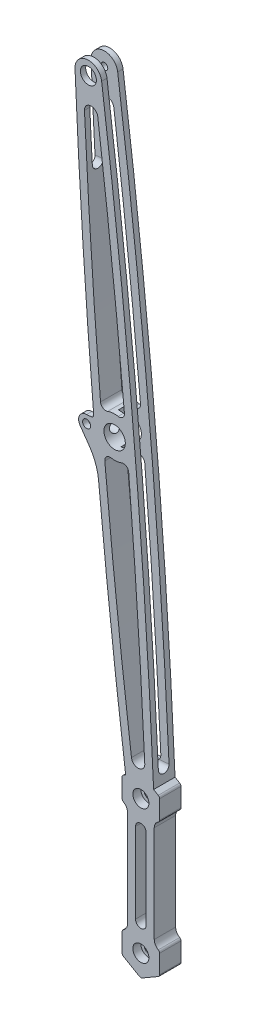
SolidWorks part; units mm, degrees
material "A2017"
ref_plane "正面" through (0, 0, 0) normal (0, 0, 1) x (1, 0, 0)
ref_plane "平面" through (0, 0, 0) normal (0, 1, 0) x (1, 0, 0)
ref_plane "右側面" through (0, 0, 0) normal (1, 0, 0) x (0, 0, -1)
sketch "ｽｹｯﾁ1" plane through (0, 0, 0) normal (0, 0, 1) x (1, 0, 0)
  line L0 (0, 0) -> (9.0749, 0) construction
  line L1 (0, 25) -> (0, 0) construction
  line L2 (0, -16.9171) -> (7, -20.9585)
  line L3 (7, 20.9585) -> (7, 29.0415)
  line L4 (7, 29.0415) -> (0, 33.0829)
  line L5 (0, 33.0829) -> (-7, 29.0415)
  line L6 (-7, 29.0415) -> (-7, 20.9585)
  line L7 (-7, 20.9585) -> (0, 16.9171)
  line L8 (0, 16.9171) -> (7, 20.9585)
  line L9 (-7, -20.9585) -> (0, -16.9171)
  line L10 (-7, -29.0415) -> (-7, -20.9585)
  line L11 (0, -33.0829) -> (-7, -29.0415)
  line L12 (7, -29.0415) -> (0, -33.0829)
  line L13 (7, -20.9585) -> (7, -29.0415)
  circle A0 centre (0, 25) radius 3
  circle A1 centre (0, -25) radius 3
  circle A2 centre (0, 25) radius 7 construction
  circle A3 centre (0, -25) radius 7 construction
  dimension "D1" = 6
  dimension "D2" = 50
  dimension "D3" = 14
extrude "ﾎﾞｽ - 押し出し1" add sketch "ｽｹｯﾁ1" along normal mid plane 8
sketch "ｽｹｯﾁ2" plane through (0, 0, 4) normal (0, 0, 1) x (1, 0, 0)
  line L0 (-7, 20.9585) -> (0, 16.9171) construction
  line L1 (5, -19.8038) -> (-5, -19.8038)
  line L2 (5, -19.8038) -> (5, 19.8038)
  line L3 (5, 19.8038) -> (-5, 19.8038)
  line L4 (-5, -19.8038) -> (-5, 19.8038)
  line L5 (5, -19.8038) -> (-5, 19.8038) construction
  line L6 (5, 19.8038) -> (-5, -19.8038) construction
  point P0 (0, 0)
  dimension "D1" = 10
extrude "ﾎﾞｽ - 押し出し2" add sketch "ｽｹｯﾁ2" against normal up to surface (8 mm away) up to face at (0, 25, -4)
fillet "ﾌｨﾚｯﾄ1" radius 3 4 edges at (5, -19.8038, 0) (-5, 19.8038, 0) (-5, -19.8038, 0) (5, 19.8038, 0)
fillet "ﾌｨﾚｯﾄ2" radius 1 10 edges at (-7, 20.9585, 0) (-7, 29.0415, 0) (0, 33.0829, 0) (7, 29.0415, 0) (7, 20.9585, 0) (7, -29.0415, 0) (0, -33.0829, 0) (-7, -29.0415, 0) (-7, -20.9585, 0) (7, -20.9585, 0)
sketch "ｽｹｯﾁ3" plane through (0, 0, -4) normal (0, 0, -1) x (-1, 0, 0)
  line L0 (0, -15) -> (0, 15) construction
  line L1 (-2, -15) -> (-2, 15)
  line L2 (2, -15) -> (2, 15)
  arc A0 (-2, -15) -> (2, -15) centre (0, -15) ccw
  arc A1 (2, 15) -> (-2, 15) centre (0, 15) ccw
  point P2 (0, 0)
  dimension "D1" = 4
  dimension "D2" = 30
extrude "ｶｯﾄ - 押し出し1" cut sketch "ｽｹｯﾁ3" against normal up to surface (8 mm away) up to face at (0, 0, 4)
sketch "ｽｹｯﾁ5" plane through (0, 0, 4) normal (0, 0, 1) x (1, 0, 0)
  circle A0 centre (0, -25) radius 3 construction
  circle A1 centre (0, 25) radius 3 construction
  circle A2 centre (0, -25) radius 3
  circle A3 centre (0, 25) radius 3
extrude "ﾎﾞｽ - 押し出し3" [suppressed] add sketch "ｽｹｯﾁ5" against normal blind 5
sketch "ｽｹｯﾁ8" plane through (0, 0, -4) normal (0, 0, -1) x (-1, 0, 0)
  circle A0 centre (0, -25) radius 3 construction
  circle A1 centre (0, 25) radius 3 construction
  circle A2 centre (0, -25) radius 3
  circle A3 centre (0, 25) radius 3
extrude "ﾎﾞｽ - 押し出し4" add sketch "ｽｹｯﾁ8" against normal blind 5
hole_wizard "M3 すきま穴1" positions "ｽｹｯﾁ6" profile "ｽｹｯﾁ7" hole size "M3" standard "JIS" end condition through all
sketch "ｽｹｯﾁ6" plane through (0, 0, 4) normal (0, 0, -1) x (-1, 0, 0)
  point P0 (0, 25)
  point P3 (0, -25)
sketch "ｽｹｯﾁ7" plane through (0, 25, 4) normal (1, 0, 0) x (0, -1, 0)
  line L0 (0, 0) -> (0, 8)
  line L1 (0, 8) -> (1.7, 8)
  line L2 (1.7, 8) -> (1.7, 0)
  line L5 (1.7, 0) -> (0, 0)
  line L11 (0, -6.35) -> (0, 107.95) construction
  dimension "通し穴の直径" = 3.4
  dimension "通し穴の深さ" = 8
sketch "ｽｹｯﾁ9" plane through (0, 0, 4) normal (0, 0, 1) x (1, 0, 0)
  line L0 (0, 25) -> (0, 298.9535) construction
  line L1 (0, 25) -> (-19.61, 249.1438) construction
  line L2 (0, 25) -> (-19.61, 249.1438) construction
  line L3 (-7.4715, 24.3463) -> (-27.0815, 248.4901) construction
  line L4 (7.4715, 25.6537) -> (-12.1386, 249.7975) construction
  line L15 (-7, 28.4641) -> (-7, 21.5359)
  line L16 (-5, 18.0718) -> (-5, -18.0718)
  line L17 (-7, -21.5359) -> (-7, -28.4641)
  line L18 (-6.5, -29.3301) -> (-0.5, -32.7942)
  line L19 (0.5, -32.7942) -> (6.5, -29.3301)
  line L20 (7, -28.4641) -> (7, -21.5359)
  line L21 (5, -18.0718) -> (5, 18.0718)
  line L22 (7, 21.5359) -> (7, 28.4641)
  line L23 (6.5, 29.3301) -> (0.5, 32.7942)
  line L24 (-0.5, 32.7942) -> (-6.5, 29.3301)
  line L25 (-7, 28.4641) -> (-7, 21.5359)
  line L26 (-5, 18.0718) -> (-5, -18.0718)
  line L27 (-7, -21.5359) -> (-7, -28.4641)
  line L28 (-6.5, -29.3301) -> (-0.5, -32.7942)
  line L29 (0.5, -32.7942) -> (6.5, -29.3301)
  line L30 (7, -28.4641) -> (7, -21.5359)
  line L31 (5, -18.0718) -> (5, 18.0718)
  line L32 (7, 21.5359) -> (7, 28.4641)
  line L33 (6.5, 29.3301) -> (0.5, 32.7942)
  line L34 (-0.5, 32.7942) -> (-6.5, 29.3301)
  arc A0 (-7.4715, 24.3463) -> (7.4715, 25.6537) centre (0, 25) ccw construction
  arc A1 (-12.1386, 249.7975) -> (-27.0815, 248.4901) centre (-19.61, 249.1438) ccw construction
  circle A2 centre (-19.61, 249.1438) radius 5 construction
  circle A3 centre (0, 25) radius 5
  arc A4 (-14.6533, 249.8004) -> (4.9954, 25.2141) centre (-2530.1776, -83.4321) cw
  arc A5 (-24.6055, 248.9297) -> (-4.9567, 24.3434) centre (2510.5676, 357.5759) ccw
  arc A6 (-14.6533, 249.8004) -> (-24.6055, 248.9297) centre (-19.61, 249.1438) ccw
  arc A16 (-7, 21.5359) -> (-6.5, 20.6699) centre (-6, 21.5359) ccw
  arc A17 (-5, 18.0718) -> (-6.5, 20.6699) centre (-8, 18.0718) ccw
  arc A18 (-6.5, -20.6699) -> (-5, -18.0718) centre (-8, -18.0718) ccw
  arc A19 (-6.5, -20.6699) -> (-7, -21.5359) centre (-6, -21.5359) ccw
  arc A20 (-7, -28.4641) -> (-6.5, -29.3301) centre (-6, -28.4641) ccw
  arc A21 (-0.5, -32.7942) -> (0.5, -32.7942) centre (0, -31.9282) ccw
  arc A22 (6.5, -29.3301) -> (7, -28.4641) centre (6, -28.4641) ccw
  arc A23 (7, -21.5359) -> (6.5, -20.6699) centre (6, -21.5359) ccw
  arc A24 (5, -18.0718) -> (6.5, -20.6699) centre (8, -18.0718) ccw
  arc A25 (6.5, 20.6699) -> (5, 18.0718) centre (8, 18.0718) ccw
  arc A26 (6.5, 20.6699) -> (7, 21.5359) centre (6, 21.5359) ccw
  arc A27 (7, 28.4641) -> (6.5, 29.3301) centre (6, 28.4641) ccw
  arc A28 (0.5, 32.7942) -> (-0.5, 32.7942) centre (0, 31.9282) ccw
  arc A29 (-6.5, 29.3301) -> (-7, 28.4641) centre (-6, 28.4641) ccw
  arc A30 (-7, 21.5359) -> (-6.5, 20.6699) centre (-6, 21.5359) ccw
  arc A31 (-5, 18.0718) -> (-6.5, 20.6699) centre (-8, 18.0718) ccw
  arc A32 (-6.5, -20.6699) -> (-5, -18.0718) centre (-8, -18.0718) ccw
  arc A33 (-6.5, -20.6699) -> (-7, -21.5359) centre (-6, -21.5359) ccw
  arc A34 (-7, -28.4641) -> (-6.5, -29.3301) centre (-6, -28.4641) ccw
  arc A35 (-0.5, -32.7942) -> (0.5, -32.7942) centre (0, -31.9282) ccw
  arc A36 (6.5, -29.3301) -> (7, -28.4641) centre (6, -28.4641) ccw
  arc A37 (7, -21.5359) -> (6.5, -20.6699) centre (6, -21.5359) ccw
  arc A38 (5, -18.0718) -> (6.5, -20.6699) centre (8, -18.0718) ccw
  arc A39 (6.5, 20.6699) -> (5, 18.0718) centre (8, 18.0718) ccw
  arc A40 (6.5, 20.6699) -> (7, 21.5359) centre (6, 21.5359) ccw
  arc A41 (7, 28.4641) -> (6.5, 29.3301) centre (6, 28.4641) ccw
  arc A42 (0.5, 32.7942) -> (-0.5, 32.7942) centre (0, 31.9282) ccw
  arc A43 (-6.5, 29.3301) -> (-7, 28.4641) centre (-6, 28.4641) ccw
  point P4 (-9.805, 137.0719)
  arc M28 (0.5, 32.7942) -> (-0.5, 32.7942) centre (0, 31.9282) ccw
  line M29 (-0.5, 32.7942) -> (-6.5, 29.3301)
  dimension "D5" = 10
  dimension "D1" = 5
  dimension "D2" = 225
  dimension "D4" = 15
  dimension "D3" = 0
extrude "ﾎﾞｽ - 押し出し5" add sketch "ｽｹｯﾁ9" against normal up to surface (8 mm away) contours A4 A6 A5 L33 M29 M28 region at (-10.1534, 141.0541, 4) up to face at (1.7, 25, -4)
sketch "ｽｹｯﾁ12" plane through (0, 0, -4) normal (0, 0, -1) x (-1, 0, 0)
  line L0 (19.61, 249.1438) -> (0, 25) construction
hole_wizard "M3 ねじ穴1" positions "ｽｹｯﾁ19" profile "ｽｹｯﾁ20" tap size "M3" standard "JIS" end condition through all
sketch "ｽｹｯﾁ19" plane through (0, 0, 4) normal (0, 0, 1) x (1, 0, 0)
  point P0 (-19.61, 249.1438)
sketch "ｽｹｯﾁ20" plane through (-19.61, 249.1438, 4) normal (1, 0, 0) x (0, -1, 0)
  line L0 (0, 0) -> (0, 8)
  line L1 (0, 8) -> (1.25, 8)
  line L2 (1.25, 8) -> (1.25, 0)
  line L5 (1.25, 0) -> (0, 0)
  line L11 (0, -6.35) -> (0, 107.95) construction
  dimension "次ｻｰﾌｪｽまでのねじ下穴ﾄﾞﾘﾙ直径" = 2.5
  dimension "次ｻｰﾌｪｽまでのねじ下穴ﾄﾞﾘﾙの深さ" = 8
cosmetic thread "穴のねじ山1" parameters "D2"=3
sketch "ｽｹｯﾁ10" plane through (0, 0, 4) normal (0, 0, 1) x (1, 0, 0)
  circle A0 centre (-19.61, 249.1438) radius 3
  dimension "D1" = 6
extrude "ｶｯﾄ - 押し出し2" cut sketch "ｽｹｯﾁ10" against normal blind 6
sketch "ｽｹｯﾁ21" plane through (0, 0, -4) normal (0, 0, -1) x (-1, 0, 0)
  circle A0 centre (19.61, 249.1438) radius 3
  dimension "D1" = 6
extrude "ｶｯﾄ - 押し出し8" [suppressed] cut sketch "ｽｹｯﾁ21" against normal blind 6
ref_plane "平面1" through (2.1706, 0.1899, 0) normal (0.9962, 0.0872, 0) x (0.0872, -0.9962, 0)
sketch "ｽｹｯﾁ13" plane through (0, 0, -4) normal (0, 0, -1) x (-1, 0, 0)
  line L0 (19.61, 249.1438) -> (0, 25) construction
  arc A2 (17.6274, 249.4065) -> (-1.7741, 30.1938) centre (2530.1776, -83.4321) ccw
  arc A3 (17.6274, 249.4065) -> (-1.7741, 30.1938) centre (2530.1776, -83.4321) ccw
  arc A4 (21.0716, 237.1884) -> (16.0946, 237.6238) centre (18.5745, 237.3071) ccw
  arc A5 (2.6995, 30.1943) -> (21.6082, 249.0582) centre (-2510.5676, 357.5759) ccw
  arc A6 (2.6995, 30.1943) -> (21.6082, 249.0582) centre (-2510.5676, 357.5759) ccw
  arc A7 (-1.4616, 36.9554) -> (3.5154, 36.52) centre (1.0356, 36.8367) ccw
  dimension "D3" = 5
  dimension "D1" = 3
  dimension "D2" = 3
extrude "ｶｯﾄ - 押し出し3" cut sketch "ｽｹｯﾁ13" against normal through all contours A3 A7 A6 A4 region at (-9.805, 137.0719, -4)
sketch "ｽｹｯﾁ14" plane through (0, 0, -4) normal (0, 0, -1) x (-1, 0, 0)
  line L0 (14.2879, 136.6797) -> (5.3221, 137.4641) construction
  arc A0 (3.5154, 36.52) -> (21.0716, 237.1884) centre (-2510.5676, 357.5759) ccw construction
  arc A1 (16.0946, 237.6238) -> (-1.4616, 36.9554) centre (2530.1776, -83.4321) ccw construction
  circle A2 centre (9.805, 137.0719) radius 7.5
  arc A3 (5.6744, 29.8068) -> (24.6055, 248.9297) centre (-2510.5676, 357.5759) ccw construction
extrude "ﾎﾞｽ - 押し出し6" add sketch "ｽｹｯﾁ14" against normal up to surface (8 mm away) up to face at (-9.805, 137.0719, 4)
fillet "ﾌｨﾚｯﾄ3" radius 2 4 edges at (-4.8058, 131.481, 0) (-13.7574, 130.6978, 0) (-14.8042, 142.6628, 0) (-5.8526, 143.446, 0)
sketch "ｽｹｯﾁ15" plane through (0, 0, 4) normal (0, 0, 1) x (1, 0, 0)
  line L0 (-19.61, 249.1438) -> (0, 25) construction
  circle A0 centre (-9.805, 137.0719) radius 4
  dimension "D1" = 8
extrude "ｶｯﾄ - 押し出し4" cut sketch "ｽｹｯﾁ15" against normal through all
sketch "ｽｹｯﾁ16" plane through (2.1706, 0.1899, 0) normal (0.9962, 0.0872, 0) x (0.0872, -0.9962, 0)
  line L0 (-254.9049, 0) -> (-34.9049, 0) construction
  line L1 (-254.9049, 4) -> (-254.9049, -4) construction
  line L2 (-254.9049, 2) -> (-34.9049, 2)
  line L3 (-254.9049, -2) -> (-34.9049, -2)
  arc A0 (-254.9049, 2) -> (-254.9049, -2) centre (-254.9049, 0) ccw
  arc A1 (-34.9049, -2) -> (-34.9049, 2) centre (-34.9049, 0) ccw
  point P5 (-144.9049, 0)
  dimension "D1" = 4
  dimension "D2" = 220
extrude "ｶｯﾄ - 押し出し6" cut sketch "ｽｹｯﾁ16" along normal through all
sketch "ｽｹｯﾁ22" plane through (2.1706, 0.1899, 0) normal (0.9962, 0.0872, 0) x (0, 0, -1)
  line L0 (0, 254.9049) -> (0, 219.9049) construction
  line L1 (-2, 254.9049) -> (2, 254.9049) construction
  line L2 (2, 254.9049) -> (2, 219.9049)
  line L3 (-2, 254.9049) -> (-2, 219.9049)
  line L4 (2, 252.9049) -> (2, 254.9049) construction
  arc A0 (2, 254.9049) -> (-2, 254.9049) centre (0, 254.9049) ccw
  arc A1 (-2, 219.9049) -> (2, 219.9049) centre (0, 219.9049) ccw
  point P5 (0, 237.4049)
  dimension "D1" = 35
extrude "ｶｯﾄ - 押し出し9" cut sketch "ｽｹｯﾁ22" against normal through all
sketch "ｽｹｯﾁ23" plane through (2.1706, 0.1899, 0) normal (0.9962, 0.0872, 0) x (0, 0, -1)
  line L0 (0, 129.9049) -> (0, 144.9049) construction
  line L1 (2, 129.9049) -> (-2, 129.9049) construction
  line L2 (-2, 144.9049) -> (2, 144.9049) construction
  circle A0 centre (0, 137.4049) radius 2
  dimension "D1" = 4
extrude "ｶｯﾄ - 押し出し10" cut sketch "ｽｹｯﾁ23" against normal through all
sketch "ｽｹｯﾁ24" plane through (0, 0, 4) normal (0, 0, 1) x (1, 0, 0)
  line L0 (-9.805, 137.0719) -> (0, 25) construction
  line L1 (-20.2651, 136.1568) -> (-9.805, 137.0719) construction
  line L2 (-20.2651, 139.1568) -> (-17.5352, 139.3956)
  line L3 (-22.7225, 134.436) -> (-16.2721, 125.2239)
  line L14 (6.5, 29.3301) -> (4.7711, 30.3283)
  line L15 (-5.6744, 29.8068) -> (-6.5, 29.3301)
  line L16 (-7, 28.4641) -> (-7, 21.5359)
  line L17 (-5, 18.0718) -> (-5, -18.0718)
  line L18 (-7, -21.5359) -> (-7, -28.4641)
  line L19 (-6.5, -29.3301) -> (-0.5, -32.7942)
  line L20 (0.5, -32.7942) -> (6.5, -29.3301)
  line L21 (7, -28.4641) -> (7, -21.5359)
  line L22 (5, -18.0718) -> (5, 18.0718)
  line L23 (7, 21.5359) -> (7, 28.4641)
  line L24 (6.5, 29.3301) -> (4.7711, 30.3283)
  line L25 (-5.6744, 29.8068) -> (-6.5, 29.3301)
  line L26 (-7, 28.4641) -> (-7, 21.5359)
  line L27 (-5, 18.0718) -> (-5, -18.0718)
  line L28 (-7, -21.5359) -> (-7, -28.4641)
  line L29 (-6.5, -29.3301) -> (-0.5, -32.7942)
  line L30 (0.5, -32.7942) -> (6.5, -29.3301)
  line L31 (7, -28.4641) -> (7, -21.5359)
  line L32 (5, -18.0718) -> (5, 18.0718)
  line L33 (7, 21.5359) -> (7, 28.4641)
  circle A0 centre (-20.2651, 136.1568) radius 1.5
  circle A1 centre (-20.2651, 136.1568) radius 3
  arc A2 (-24.6055, 248.9297) -> (-5.6744, 29.8068) centre (2510.5676, 357.5759) ccw construction
  arc A19 (4.7711, 30.3283) -> (-14.6533, 249.8004) centre (-2530.1776, -83.4321) ccw
  arc A20 (-14.6533, 249.8004) -> (-24.6055, 248.9297) centre (-19.61, 249.1438) ccw
  arc A21 (-24.6055, 248.9297) -> (-5.6744, 29.8068) centre (2510.5676, 357.5759) ccw
  arc A22 (-6.5, 29.3301) -> (-7, 28.4641) centre (-6, 28.4641) ccw
  arc A23 (-7, 21.5359) -> (-6.5, 20.6699) centre (-6, 21.5359) ccw
  arc A24 (-5, 18.0718) -> (-6.5, 20.6699) centre (-8, 18.0718) ccw
  arc A25 (-6.5, -20.6699) -> (-5, -18.0718) centre (-8, -18.0718) ccw
  arc A26 (-6.5, -20.6699) -> (-7, -21.5359) centre (-6, -21.5359) ccw
  arc A27 (-7, -28.4641) -> (-6.5, -29.3301) centre (-6, -28.4641) ccw
  arc A28 (-0.5, -32.7942) -> (0.5, -32.7942) centre (0, -31.9282) ccw
  arc A29 (6.5, -29.3301) -> (7, -28.4641) centre (6, -28.4641) ccw
  arc A30 (7, -21.5359) -> (6.5, -20.6699) centre (6, -21.5359) ccw
  arc A31 (5, -18.0718) -> (6.5, -20.6699) centre (8, -18.0718) ccw
  arc A32 (6.5, 20.6699) -> (5, 18.0718) centre (8, 18.0718) ccw
  arc A33 (6.5, 20.6699) -> (7, 21.5359) centre (6, 21.5359) ccw
  arc A34 (7, 28.4641) -> (6.5, 29.3301) centre (6, 28.4641) ccw
  arc A35 (4.7711, 30.3283) -> (-14.6533, 249.8004) centre (-2530.1776, -83.4321) ccw
  arc A36 (-14.6533, 249.8004) -> (-24.6055, 248.9297) centre (-19.61, 249.1438) ccw
  arc A37 (-24.6055, 248.9297) -> (-5.6744, 29.8068) centre (2510.5676, 357.5759) ccw
  arc A38 (-6.5, 29.3301) -> (-7, 28.4641) centre (-6, 28.4641) ccw
  arc A39 (-7, 21.5359) -> (-6.5, 20.6699) centre (-6, 21.5359) ccw
  arc A40 (-5, 18.0718) -> (-6.5, 20.6699) centre (-8, 18.0718) ccw
  arc A41 (-6.5, -20.6699) -> (-5, -18.0718) centre (-8, -18.0718) ccw
  arc A42 (-6.5, -20.6699) -> (-7, -21.5359) centre (-6, -21.5359) ccw
  arc A43 (-7, -28.4641) -> (-6.5, -29.3301) centre (-6, -28.4641) ccw
  arc A44 (-0.5, -32.7942) -> (0.5, -32.7942) centre (0, -31.9282) ccw
  arc A45 (6.5, -29.3301) -> (7, -28.4641) centre (6, -28.4641) ccw
  arc A46 (7, -21.5359) -> (6.5, -20.6699) centre (6, -21.5359) ccw
  arc A47 (5, -18.0718) -> (6.5, -20.6699) centre (8, -18.0718) ccw
  arc A48 (6.5, 20.6699) -> (5, 18.0718) centre (8, 18.0718) ccw
  arc A49 (6.5, 20.6699) -> (7, 21.5359) centre (6, 21.5359) ccw
  arc A50 (7, 28.4641) -> (6.5, 29.3301) centre (6, 28.4641) ccw
  arc M47 (-24.6055, 248.9297) -> (-5.6744, 29.8068) centre (2510.5676, 357.5759) ccw
  dimension "D1" = 3
  dimension "D2" = 6
  dimension "D3" = 30
  dimension "D4" = 0
extrude "ﾎﾞｽ - 押し出し7" add sketch "ｽｹｯﾁ24" against normal blind 2 contours A1 A0 | A1 L3 M47 | A1 L2 M47 region at (-18.2956, 138.306, 4) region at (-18.1329, 138.6707, 4) region at (-18.3583, 130.927, 4)
mirror "ﾐﾗｰ1" about plane through (0, 0, 0) normal (0, 0, 1) of "ﾎﾞｽ - 押し出し7"
fillet "ﾌｨﾚｯﾄ4" radius 20 2 edges at (-16.2721, 125.2239, -3) (-16.2721, 125.2239, 3)
fillet "ﾌｨﾚｯﾄ5" radius 1 2 edges at (-17.5352, 139.3956, -3) (-17.5352, 139.3956, 3)
